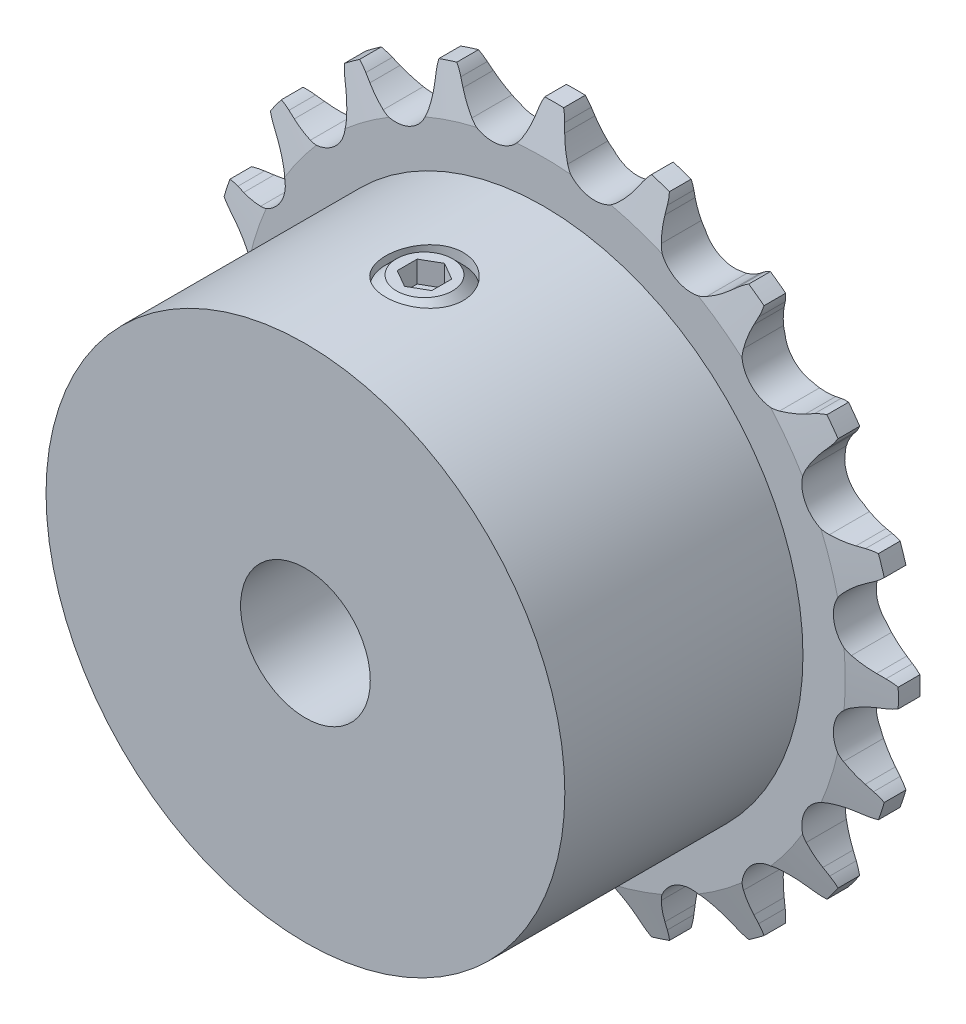
SolidWorks part; units mm, degrees
material "6061 Alloy"
ref_plane "Front Plane" through (0, 0, 0) normal (0, 0, 1) x (1, 0, 0)
ref_plane "Top Plane" through (0, 0, 0) normal (0, 1, 0) x (1, 0, 0)
ref_plane "Right Plane" through (0, 0, 0) normal (1, 0, 0) x (0, 0, -1)
sketch "Sketch0" plane through (0, 0, 0) normal (0, 0, 1) x (1, 0, 0)
  line L0 (1.8733, -11.8272) -> (0, 0) construction
  line L1 (0, 0) -> (5.4364, -10.6695) construction
  line L2 (0, 0) -> (-1.8732, -11.8272) construction
  line L3 (1.8733, -11.8272) -> (5.4364, -10.6695) construction
  line L4 (1.8733, -11.8272) -> (-1.8732, -11.8272) construction
  line L5 (3.3386, -11.8169) -> (3.189, -11.5756)
  line L6 (1.8733, -11.8272) -> (0, -12.1239) construction
  line L7 (0.4765, -12.2702) -> (0.5442, -11.9945)
  line L8 (0, -11.8272) -> (0, -12.9512) construction
  line L9 (2.6827, -10.9593) -> (0.626, -13.1647) construction
  line L10 (0, 0) -> (0, -11.8272) construction
  line L11 (3.189, -11.5756) -> (0.626, -13.1647) construction
  line L12 (0, -12.9512) -> (0, -13.1264) construction
  line L13 (4.917, -10.8383) -> (3.3386, -11.8169) construction
  circle A0 centre (0, 0) radius 12.9512 construction
  circle A1 centre (0, 0) radius 11.9747 construction
  arc A2 (-1.5343, -13.6729) -> (5.6843, -12.5296) centre (0, 0) ccw
  circle A3 centre (0, 0) radius 13.1264 construction
  circle A4 centre (1.8733, -11.8272) radius 1.143 construction
  arc A7 (2.6827, -10.9593) -> (0.8352, -11.2519) centre (1.8733, -11.8272) ccw
  circle A8 centre (1.8733, -11.8272) radius 1.1868 construction
  arc A9 (3.3386, -11.8169) -> (5.6843, -12.5296) centre (4.917, -10.8383) ccw
  arc A10 (3.189, -11.5756) -> (2.6827, -10.9593) centre (0.626, -13.1647) ccw
  arc A11 (0.4765, -12.2702) -> (-1.5343, -13.6729) centre (-1.3271, -11.8272) cw
  arc A12 (0.5442, -11.9945) -> (0.8352, -11.2519) centre (3.4728, -12.7139) cw
  dimension "D1" = 1.1868
  dimension "Dr" = 2.286
  dimension "Ds" = 2.3736
  dimension "R" = 1.1868
  dimension "Pitch" = 3.7465
  dimension "A" = 38
  dimension "360/N" = 18
  dimension "B" = 15.2
  dimension "ab" = 3.2004
  dimension "J" = 1.1239
  dimension "ac" = 1.8288
sketch "Sketch1" plane through (0, 0, 0) normal (1, 0, 0) x (0, 0, -1)
  line L0 (0.7874, 0) -> (-0.7874, 0)
  line L1 (-0.7874, 0) -> (-0.7874, 11.0779)
  line L2 (-0.7874, 11.0779) -> (-0.3191, 12.9512)
  line L3 (-0.3191, 12.9512) -> (0.3191, 12.9512)
  line L4 (0.3191, 12.9512) -> (0.7874, 11.0779)
  line L5 (0.7874, 11.0779) -> (0.7874, 0)
  line L7 (0, 12.9512) -> (0, 0) construction
  line L8 (-0.7874, 11.0779) -> (0.7874, 11.0779) construction
  line L9 (0, 12.9512) -> (0, -12.9512) construction
  line L10 (-0.7874, 11.0779) -> (-0.7874, 12.9512) construction
  line L11 (-0.7874, 12.9512) -> (-0.3191, 12.9512) construction
  line L12 (0.3191, 12.9512) -> (0.7874, 12.9512) construction
  line L13 (0.7874, 12.9512) -> (0.7874, 11.0779) construction
  line L22 (0.7874, 0) -> (-9.5313, 0) construction
  line L24 (-0.7874, 0) -> (-0.7874, 9.573) construction
  dimension "t" = 1.5748
  dimension "g" = 0.4683
  dimension "h" = 1.8732
  dimension "MHD" = 19.146
  dimension "Width" = 10.3187
revolve "Revolve1" add sketch "Sketch1" angle 360 mid plane about L0
extrude "Cut-Extrude1" cut sketch "Sketch0" against normal through all and the other way through all
pattern_circular "CirPattern1" count 20 over 360 about axis through (0, 0, -0.7874) along (0, 0, -1) of "Cut-Extrude1"
sketch "Sketch2" plane through (0, 0, 0) normal (0, 0, 1) x (1, 0, 0)
  line L0 (0, 0) -> (0, 9.525) construction
  circle A0 centre (0, 0) radius 2.3813 construction
  circle A1 centre (0, 0) radius 9.525
  circle A2 centre (0, 0) radius 12.6365 construction
  dimension "Bore" = 4.7625
  dimension "Hub Dia." = 19.05
  dimension "OD" = 25.273
extrude "Boss-Extrude1" add sketch "Sketch2" along normal up to vertex (9.5313 mm away) from surface up to point (0, 0, 9.5313) starting at face at (0, 0, 0.7874)
sketch "Sketch3" plane through (0, 0, 0) normal (0, 0, 1) x (1, 0, 0)
  circle A0 centre (0, 0) radius 2.3813 construction
  circle A1 centre (0, 0) radius 2.3813
  circle A2 centre (0, 0) radius 12.6365 construction
  circle A3 centre (0, 0) radius 12.6365
extrude "Cut-Extrude2" cut sketch "Sketch3" along normal through all and the other way through all flip side to cut
sketch "Sketch4" plane through (0, 0, 0) normal (1, 0, 0) x (0, 0, -1)
  line L1 (-0.7874, 12.9512) -> (-3.1686, 12.9512)
  line L2 (-0.7874, 12.9512) -> (-0.7874, 9.573)
  line L3 (-0.7874, 9.573) -> (-3.1686, 9.573)
  line L4 (-3.1686, 12.9512) -> (-3.1686, 9.573)
  dimension "D1" = 2.3813
revolve "Cut-Revolve1" [suppressed] cut sketch "Sketch4" angle 360 mid plane about L22
ref_plane "Plane1" through (0, 9.525, 0) normal (0, 1, 0) x (-1, 0, 0)
sketch "Sketch5" plane through (0, 9.525, 0) normal (0, 1, 0) x (-1, 0, 0)
  line L0 (0, 0) -> (0, 0.7874) construction
  line L1 (0, 9.5313) -> (0, 0.7874) construction
  line L2 (9.525, 0.7874) -> (-9.525, 0.7874) construction
  line L3 (2.3813, 9.5313) -> (-2.3813, 9.5313) construction
  circle A0 centre (0, 5.1594) radius 1.4224
  circle A1 centre (0, 5.1594) radius 0.7874 construction
  circle A2 centre (0, 5.1594) radius 1.0255 construction
  dimension "D1" = 0.3969
  dimension "Screw OD" = 2.8448
  dimension "Pitch" = 0.635
extrude "Cut-Extrude3" cut sketch "Sketch5" against normal up to surface (9.525 mm away) up to plane "Top Plane"
sketch "Sketch6" plane through (0, 0, 0) normal (1, 0, 0) x (0, 0, -1)
  line L0 (-5.1594, 9.525) -> (-5.1594, 2.3813)
  line L1 (-5.1594, 2.3813) -> (-6.1849, 2.3812)
  line L2 (-6.1849, 2.3812) -> (-6.5818, 2.7781)
  line L3 (-6.5818, 2.7781) -> (-6.5818, 9.1281)
  line L4 (-6.5818, 9.1281) -> (-6.1849, 9.525)
  line L5 (-6.1849, 9.525) -> (-5.1594, 9.525)
  line L6 (-5.1594, 2.3813) -> (-5.1594, 0) construction
  line L7 (-5.1594, 0) -> (0, 0) construction
  line L10 (-6.5818, 2.3813) -> (-9.5313, 2.3813) construction
  line L11 (-6.5818, 9.1281) -> (-6.5818, 9.525) construction
  line L12 (-6.5818, 9.525) -> (-6.1849, 9.525) construction
revolve "Revolve2" add sketch "Sketch6" angle 360 mid plane about L6
sketch "Sketch7" plane through (0, 9.525, 0) normal (0, 1, 0) x (1, 0, 0)
  line L1 (0, -4.4261) -> (-0.635, -4.7928)
  line L2 (-0.635, -4.7928) -> (-0.635, -5.526)
  line L3 (-0.635, -5.526) -> (0, -5.8926)
  line L4 (0, -5.8926) -> (0.635, -5.526)
  line L5 (0.635, -5.526) -> (0.635, -4.7928)
  line L6 (0.635, -4.7928) -> (0, -4.4261)
  circle A0 centre (0, -5.1594) radius 0.635 construction
  dimension "Hex" = 1.27
extrude "Cut-Extrude4" cut sketch "Sketch7" against normal blind 0.7937
equation "\"360/N@Sketch0\" = 360/\"Teeth@CirPattern1\""
equation "\"Ds@Sketch0\" = 1.005 * \"Dr@Sketch0\" + 0.003"
equation "\"R@Sketch0\" = 1/2 * \"Ds@Sketch0\""
equation "\"A@Sketch0\" = 35 +  ( 60 / \"Teeth@CirPattern1\" ) "
equation "\"B@Sketch0\" = 18 -  ( 56 / \"Teeth@CirPattern1\" )"
equation "\"ac@Sketch0\" = 0.8 * \"Dr@Sketch0\""
equation "\"ab@Sketch0\" = 1.4 * \"Dr@Sketch0\""
equation "\"J@Sketch0\" = 0.3 * \"Pitch@Sketch0\""
equation "\"h@Sketch1\" = \"Pitch@Sketch0\" / 2"
equation "\"g@Sketch1\" = \"h@Sketch1\" / 4"
equation "\"MHD@Sketch1\" = \"Pitch@Sketch0\" * ( cotan ( 180 / \"Teeth@CirPattern1\" ) - 1 ) - 0.030"
equation "\"D1@Cut-Extrude4\" = \"Hex@Sketch7\" * 5 / 8"
equation "\"D1@Sketch5\" = \"Pitch@Sketch5\" * 5 / 8"
